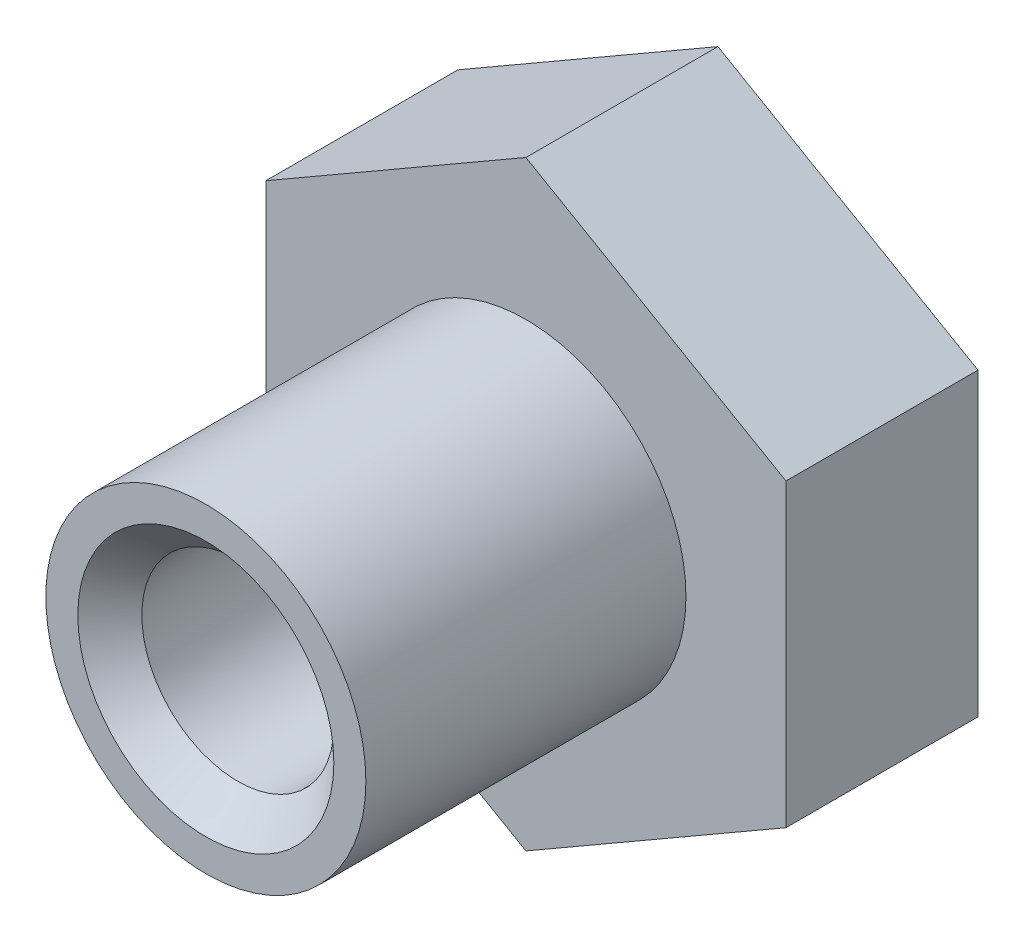
SolidWorks part; units mm, degrees
ref_plane "XY" through (0, 0, 0) normal (0, 0, 1) x (1, 0, 0)
ref_plane "XZ" through (0, 0, 0) normal (0, 1, 0) x (1, 0, 0)
ref_plane "YZ" through (0, 0, 0) normal (1, 0, 0) x (0, 0, -1)
ref_axis "X" through (-11.3506, 0, 0) along (1, 0, 0)
ref_axis "Y" through (0, -13.1066, 0) along (0, 1, 0)
ref_axis "Z" through (0, 0, 16.002) along (0, 0, -1)
sketch "Sketch1" plane through (0, 0, 0) normal (0, 0, 1) x (1, 0, 0)
  line L1 (10.3187, 5.9575) -> (0, 11.9151)
  line L2 (0, 11.9151) -> (-10.3187, 5.9575)
  line L3 (-10.3187, 5.9575) -> (-10.3187, -5.9575)
  line L4 (-10.3187, -5.9575) -> (0, -11.9151)
  line L5 (0, -11.9151) -> (10.3187, -5.9575)
  line L6 (10.3187, -5.9575) -> (10.3187, 5.9575)
  circle A0 centre (0, 0) radius 10.3187 construction
  dimension "D1" = 20.6375
extrude "Boss-Extrude1" add sketch "Sketch1" along normal blind 7.62
sketch "Sketch2" plane through (0, 0, 7.62) normal (0, 0, 1) x (1, 0, 0)
  circle A0 centre (0, 0) radius 6.35
  dimension "D1" = 12.7
extrude "Boss-Extrude2" add sketch "Sketch2" along normal blind 12.7
sketch "Sketch3" plane through (0, 0, 20.32) normal (0, 0, 1) x (1, 0, 0)
  circle A0 centre (0, 0) radius 3.81
  circle A1 centre (0, 0) radius 6.35 construction
  dimension "D1" = 2.54
extrude "Cut-Extrude1" cut sketch "Sketch3" against normal through all
chamfer "Chamfer1" distance 1.27 angle 45 2 edges at (3.81, 0, 0) (3.81, 0, 20.32)
